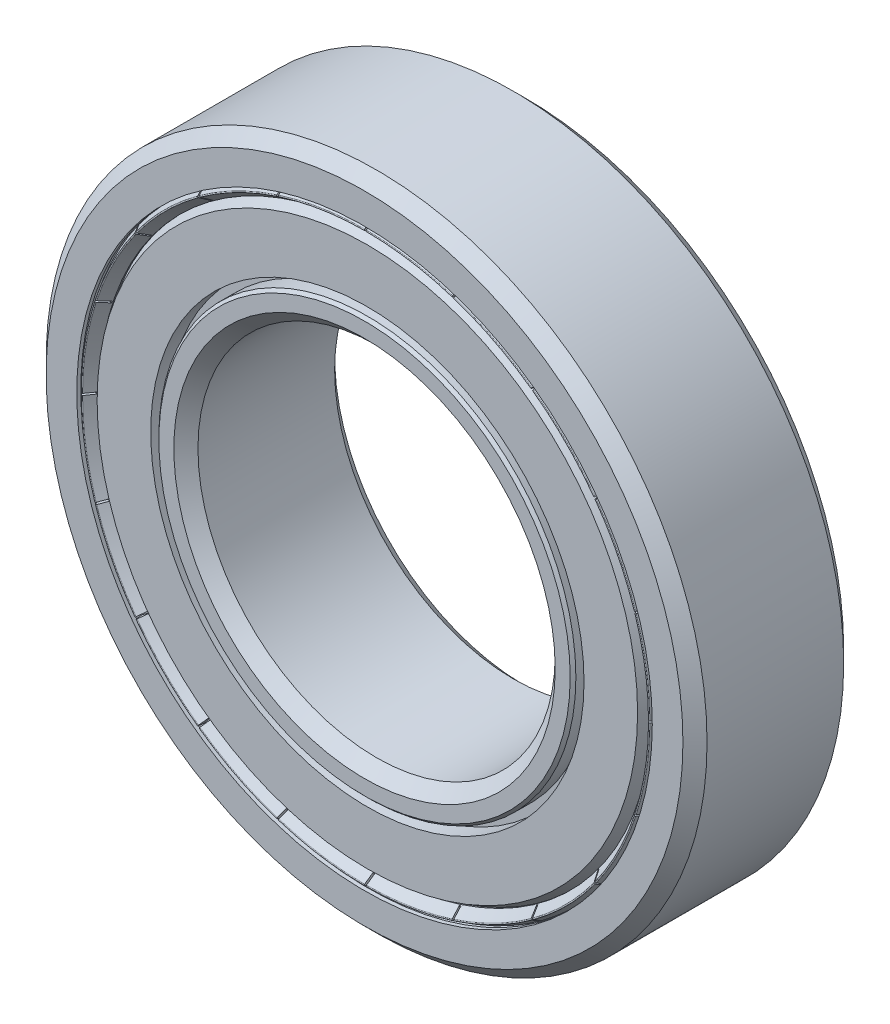
SolidWorks part; units mm, degrees
ref_plane "Front Plane" through (0, 0, 0) normal (0, 0, 1) x (1, 0, 0)
ref_plane "Top Plane" through (0, 0, 0) normal (0, 1, 0) x (1, 0, 0)
ref_plane "Right Plane" through (0, 0, 0) normal (1, 0, 0) x (0, 0, -1)
sketch "Sketch1" plane through (0, 0, 0) normal (0, 0, 1) x (1, 0, 0)
  circle A0 centre (0, 0) radius 10
  circle A1 centre (0, 0) radius 18.5
  dimension "OD" = 37
  dimension "ID" = 20
sketch "Sketch2" plane through (0, 0, 0) normal (1, 0, 0) x (0, 0, -1)
  line L0 (-4.5, 18.5) -> (4.5, 18.5)
  line L1 (-4.5, 10) -> (-4.5, -10) construction
  line L2 (4.5, 18.5) -> (4.5, -18.5) construction
  line L3 (-4.5, 0) -> (4.5, 0) construction
  line L6 (0, 18.5) -> (0, 10) construction
  circle A0 centre (0, 14.25) radius 2.975 construction
  point P8 (0, 18.5)
  dimension "Approx. Ball Dia." = 5.95
  dimension "Width" = 9
  dimension "For Shaft Diameter" = 20
  dimension "For Housing ID" = 37
sketch "Sketch3" plane through (0, 0, 0) normal (1, 0, 0) x (0, 0, -1)
  line L0 (0, 0) -> (0, 20) construction
  line L1 (-4.5, 10) -> (-4.5, -10) construction
  line L2 (3.825, 18.5) -> (-3.825, 18.5)
  line L3 (-3.825, 18.5) -> (-4.5, 17.825)
  line L4 (-4.5, 17.825) -> (-4.5, 16.1097)
  line L5 (-4.5, 16.1097) -> (-4.275, 16.1097)
  line L6 (-4.275, 16.1097) -> (-4.275, 16.6673)
  line L7 (-4.275, 16.6673) -> (-4.1159, 16.8264)
  line L8 (-4.1159, 16.8264) -> (-1.4875, 16.8264)
  line L10 (-4.5, 18.5) -> (4.5, 18.5) construction
  line L12 (-4.275, 16.6673) -> (-4.275, 17.225) construction
  line L13 (4.1159, 16.8264) -> (1.4875, 16.8264)
  line L14 (4.275, 16.6673) -> (4.1159, 16.8264)
  line L15 (4.275, 16.1097) -> (4.275, 16.6673)
  line L16 (4.5, 16.1097) -> (4.275, 16.1097)
  line L17 (4.5, 17.825) -> (4.5, 16.1097)
  line L18 (3.825, 18.5) -> (4.5, 17.825)
  line L19 (3.825, 10) -> (-3.825, 10)
  line L20 (-3.825, 10) -> (-4.5, 10.675)
  line L21 (-4.5, 10.675) -> (-4.5, 11.5145)
  line L22 (-4.5, 11.5145) -> (-4.3409, 11.6736)
  line L23 (-4.3409, 11.6736) -> (-1.4875, 11.6736)
  line L25 (4.3409, 11.6736) -> (1.4875, 11.6736)
  line L26 (4.5, 11.5145) -> (4.3409, 11.6736)
  line L27 (4.5, 10.675) -> (4.5, 11.5145)
  line L28 (3.825, 10) -> (4.5, 10.675)
  circle A2 centre (0, 14.25) radius 2.975 construction
  arc A3 (-1.4875, 16.8264) -> (1.4875, 16.8264) centre (0, 14.25) cw
  arc A4 (-1.4875, 11.6736) -> (1.4875, 11.6736) centre (0, 14.25) ccw
  point P5 (0, 17.225)
  point P31 (0, 18.5)
  point P37 (0, 10)
  dimension "D1" = 45
  dimension "D2" = 0.225
  dimension "D3" = 2.975
  dimension "D4" = 0.675
revolve "Revolve1" add sketch "Sketch3" angle 360 about L3
sketch "Sketch4" plane through (0, 0, 0) normal (1, 0, 0) x (0, 0, -1)
  line L0 (0, 17.225) -> (0, 11.275)
  line L1 (0, 18.5) -> (0, 10) construction
  circle A0 centre (0, 14.25) radius 2.975 construction
  arc A1 (0, 11.275) -> (0, 17.225) centre (0, 14.25) cw
revolve "Revolve2" add sketch "Sketch4" angle 360 about L6
pattern_circular "CirPattern1" count 10 over 360 about axis through (0, 0, 4.5) along (0, 0, -1) of bodies 106
sketch "Sketch5" plane through (0, 0, 0) normal (1, 0, 0) x (0, 0, -1)
  line L0 (-2.975, 14.25) -> (-2.975, 11.6736) construction
  line L1 (-4.3409, 11.6736) -> (-1.4875, 11.6736) construction
  line L3 (-2.975, 11.6736) -> (-3.4303, 11.6736)
  line L4 (-3.4303, 11.6736) -> (-3.4303, 12.1289)
  line L5 (-3.4303, 12.1289) -> (-4.3409, 12.1289)
  line L6 (-4.3409, 12.1289) -> (-4.3409, 15.1286)
  line L7 (-4.3409, 15.1286) -> (-3.4303, 15.6544)
  line L8 (-3.4303, 15.6544) -> (-2.975, 15.6544)
  line L9 (-2.975, 15.6544) -> (-2.975, 11.6736)
  line L10 (0, 14.25) -> (0, 18.5) construction
  line L11 (3.4303, 15.6544) -> (2.975, 15.6544)
  line L12 (4.3409, 15.1286) -> (3.4303, 15.6544)
  line L13 (4.3409, 12.1289) -> (4.3409, 15.1286)
  line L14 (3.4303, 12.1289) -> (4.3409, 12.1289)
  line L15 (3.4303, 11.6736) -> (3.4303, 12.1289)
  line L16 (2.975, 11.6736) -> (3.4303, 11.6736)
  line L17 (2.975, 15.6544) -> (2.975, 11.6736)
  line L18 (-4.3409, 15.1286) -> (-3.8856, 15.1286) construction
  line L19 (-3.8856, 15.1286) -> (-3.4303, 15.1286) construction
  line L20 (-3.4303, 15.1286) -> (-2.975, 15.1286) construction
  line L21 (-3.4303, 15.6544) -> (-3.4303, 16.1097) construction
  circle A0 centre (0, 14.25) radius 2.975 construction
  dimension "D1" = 30
revolve "Revolve3" add sketch "Sketch5" angle 360 about L3
sketch "Sketch6" plane through (0, 0, 0) normal (1, 0, 0) x (0, 0, -1)
  line L0 (-3.7517, 16.1097) -> (-4.1062, 16.1097)
  line L1 (-4.1062, 16.1097) -> (-4.5, 15.8823)
  line L2 (-4.5, 15.8823) -> (-3.8867, 15.4529)
  line L4 (-4.3409, 15.1286) -> (-3.4303, 15.6544) construction
  line L5 (-3.7517, 15.4688) -> (-3.7517, 16.1097)
  line L6 (-4.5, 16.1097) -> (-4.275, 16.1097) construction
  line L7 (-3.8867, 15.4529) -> (-3.8417, 15.4529)
  line L8 (-3.8417, 15.4529) -> (-3.7517, 15.4688)
  line L9 (-4.5, 17.825) -> (-4.5, -17.825) construction
  line L11 (-3.8417, 15.4529) -> (-3.7967, 15.4529) construction
  line L12 (-3.7967, 15.4529) -> (-3.7517, 15.4529) construction
  point P27 (-3.929, 16.1097)
  dimension "D1" = 30
  dimension "D3" = 10
  dimension "D2" = 35
  dimension "D4" = 0.045
  dimension "D5" = 0.3937
revolve "Revolve4" add sketch "Sketch6" angle 360 about L3
fillet "Fillet1" radius 0.045 1 edges at (15.8823, 0, 4.5)
sketch "Sketch7" plane through (0, 0, 0) normal (0, 0, 1) x (1, 0, 0)
  line L0 (-0.05, 16.1097) -> (-0.05, 16.2097)
  line L1 (-0.05, 16.1097) -> (0.05, 16.1097) construction
  line L2 (-0.05, 16.1097) -> (-0.05, 15.4529)
  line L3 (-0.05, 15.4529) -> (0.05, 15.4529) construction
  line L4 (0.05, 16.1097) -> (0.05, 15.4529)
  line L5 (-0.05, 16.2097) -> (0.05, 16.2097)
  line L6 (0.05, 16.2097) -> (0.05, 16.1097)
  line L7 (-0.05, 15.4529) -> (-0.05, 15.3529)
  line L8 (-0.05, 15.3529) -> (0.05, 15.3529)
  line L9 (0.05, 15.3529) -> (0.05, 15.4529)
  dimension "D1" = 0.1
extrude "Cut-Extrude1" cut sketch "Sketch7" along normal through all from vertex starting at point (0, 16.1097, 3.929)
pattern_circular "CirPattern2" count 20 over 360 about axis through (0, 0, 4.5) along (0, 0, -1) of "Cut-Extrude1"
mirror "Mirror1" about plane through (0, 0, 0) normal (0, 0, 1) of bodies 120
equation "\"Approx. Ball Dia.@Sketch2\"=( \"OD@Sketch1\" - \"ID@Sketch1\" )  * .5 * .7"
equation "\"D2@Sketch3\"=\"Width@Sketch2\"*.025"
equation "\"D3@Sketch3\"=\"Approx. Ball Dia.@Sketch2\"*.5"
equation "\"D4@Sketch3\"=\"Width@Sketch2\"*.075"
equation "\"Approx No of Balls\"= ( pi * \"OD@Sketch1\" ) * .5 / \"Approx. Ball Dia.@Sketch2\""
equation "\"D1@CirPattern1\"=\"Approx No of Balls\""
equation "\"D4@Sketch6\"=\"D2@Sketch3\"*.2"
equation "\"D1@CirPattern2\"=\"Approx No of Balls\"*2"
equation "\"D5@Sketch6\"=\"D2@Sketch3\"*1.75"
equation "\"D1@Fillet1\"=\"d4@sketch6\""
